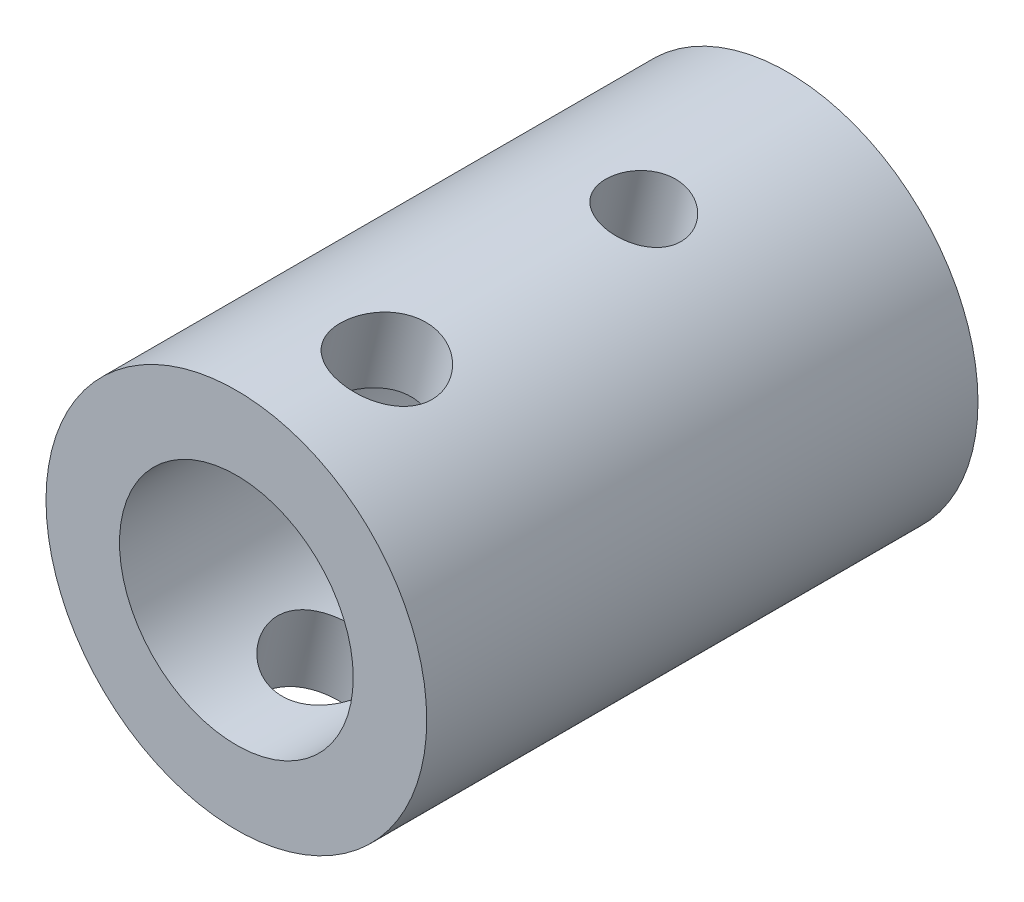
SolidWorks part; units mm, degrees
ref_plane "Front Plane" through (0, 0, 0) normal (0, 0, 1) x (1, 0, 0)
ref_plane "Top Plane" through (0, 0, 0) normal (0, 1, 0) x (1, 0, 0)
ref_plane "Right Plane" through (0, 0, 0) normal (1, 0, 0) x (0, 0, -1)
sketch "Sketch1" plane through (0, 0, 0) normal (0, 0, 1) x (1, 0, 0)
  circle A0 centre (0, 0) radius 25.9
extrude "Boss-Extrude1" add sketch "Sketch1" along normal blind 75
sketch "Sketch2" plane through (0, 0, 75) normal (0, 0, 1) x (1, 0, 0)
  circle A0 centre (0, 0) radius 15.9
extrude "Cut-Extrude1" cut sketch "Sketch2" against normal blind 75
hole_wizard "Ø10.5 (10.5) Diameter Hole1" positions "3DSketch1" profile "Sketch3" hole size "Ø10.5" standard "Ansi Metric"
sketch3d "3DSketch1"
  line L0 (0, 0, 0) -> (5.4829, 25.313, 0)
  line L3 (5.4829, 25.313, 0) -> (5.4829, 25.313, 25)
  circle A0 centre (0, 0, 0) radius 25.9 construction
  point P0 (5.4829, 25.313, 25)
  point P7 (0, 0, 25.9)
  dimension "D1" = 25
sketch "Sketch3" plane through (5.4829, 25.313, 25) normal (0, 0, 1) x (-0.9773, 0.2117, 0)
  line L0 (0, 0) -> (0, 23.1545)
  line L1 (0, 23.1545) -> (5.25, 20)
  line L2 (5.25, 20) -> (5.25, 0)
  line L5 (5.25, 0) -> (0, 0)
  line L10 (0, 23.1545) -> (-5.25, 20) construction
  line L11 (0, -6.35) -> (0, 107.95) construction
  dimension "Hole Dia." = 10.5
  dimension "Hole Depth" = 20
  dimension "Drill Angle" = 118
hole_wizard "Ø12.8 (12.8) Diameter Hole1" positions "3DSketch2" profile "Sketch4" hole size "Ø12.8" standard "Ansi Metric"
sketch3d "3DSketch2"
  line L0 (5.5559, 25.2971, 19.7505) -> (5.5559, 25.2971, 0)
  line L3 (5.5559, 25.2971, 0) -> (5.5559, 25.2971, 60)
  circle A0 centre (0, 0, 0) radius 25.9 construction
  spline S0 degree 3 poles (0.2381, 25.8989, 25.3478) (0.2381, 25.8989, 24.6522) (0.2731, 25.8987, 24.3104) (0.3755, 25.8973, 23.8062) (0.4181, 25.8967, 23.6396) (0.5203, 25.8948, 23.3094) (0.5802, 25.8936, 23.1455) (0.7815, 25.8886, 22.669) (0.9455, 25.8835, 22.3678) (1.3316, 25.8665, 21.7978) (1.5552, 25.8544, 21.5287) (2.042, 25.8205, 21.0458) (2.3071, 25.7987, 20.8288) (2.8814, 25.7408, 20.445) (3.1849, 25.7054, 20.2825) (3.6555, 25.6412, 20.0858) (3.8154, 25.618, 20.0279) (4.1411, 25.5673, 19.9277) (4.308, 25.5398, 19.8852) (4.8093, 25.4518, 19.7838) (5.1443, 25.3863, 19.7502) (5.8155, 25.241, 19.7498) (6.155, 25.1603, 19.7841) (6.8081, 24.9915, 19.9184) (7.1242, 24.903, 20.0178) (7.5831, 24.7655, 20.2157) (7.7339, 24.7188, 20.2901) (8.024, 24.6262, 20.4524) (8.1642, 24.58, 20.5405) (8.5701, 24.4427, 20.8251) (8.8229, 24.3522, 21.0431) (9.2848, 24.1798, 21.5309) (9.4891, 24.0999, 21.795) (9.8469, 23.9559, 22.3626) (10.0015, 23.8914, 22.67) (10.2483, 23.7866, 23.3044) (10.3415, 23.7459, 23.6316) (10.4678, 23.6905, 24.3063) (10.5, 23.6762, 24.6548) (10.5002, 23.676, 25.3409) (10.4693, 23.6898, 25.6826) (10.3431, 23.7452, 26.3629) (10.2491, 23.7862, 26.6927) (10.0651, 23.8644, 27.1668) (9.9965, 23.8932, 27.3218) (9.8443, 23.9563, 27.6253) (9.7603, 23.9907, 27.7744) (9.4907, 24.0993, 28.203) (9.2865, 24.1791, 28.4668) (8.8288, 24.35, 28.9512) (8.5731, 24.4417, 29.1726) (8.0314, 24.6249, 29.5529) (7.7435, 24.7174, 29.7146) (7.2844, 24.855, 29.9134) (7.1267, 24.9008, 29.9723) (6.8091, 24.9895, 30.0725) (6.6484, 25.0327, 30.1143) (6.1604, 25.159, 30.2151) (5.8253, 25.2388, 30.2498) (5.1477, 25.3857, 30.2502) (4.8125, 25.4512, 30.2165) (4.1491, 25.5677, 30.083) (3.8177, 25.6191, 29.9816) (3.1873, 25.7051, 29.7188) (2.8864, 25.7403, 29.5578) (2.4571, 25.7836, 29.2717) (2.3171, 25.7965, 29.1683) (2.05, 25.8191, 28.9503) (1.9225, 25.8288, 28.8355) (1.5574, 25.8543, 28.4738) (1.3371, 25.8662, 28.2096) (0.9468, 25.8834, 27.6348) (0.7827, 25.8885, 27.3331) (0.5153, 25.8952, 26.7018) (0.4114, 25.8968, 26.3686) (0.2731, 25.8987, 25.6911) (0.2381, 25.8989, 25.3478) (0.2381, 25.8989, 24.6522) (0.2731, 25.8987, 24.3104) knots -0.03125 -0.03125 0 0 0.03125 0.03125 0.046875 0.046875 0.0625 0.0625 0.09375 0.09375 0.125 0.125 0.15625 0.15625 0.1875 0.1875 0.203125 0.203125 0.21875 0.21875 0.25 0.25 0.28125 0.28125 0.3125 0.3125 0.328125 0.328125 0.34375 0.34375 0.375 0.375 0.40625 0.40625 0.4375 0.4375 0.46875 0.46875 0.5 0.5 0.53125 0.53125 0.5625 0.5625 0.578125 0.578125 0.59375 0.59375 0.625 0.625 0.65625 0.65625 0.6875 0.6875 0.703125 0.703125 0.71875 0.71875 0.75 0.75 0.78125 0.78125 0.8125 0.8125 0.84375 0.84375 0.859375 0.859375 0.875 0.875 0.90625 0.90625 0.9375 0.9375 0.96875 0.96875 1 1 1.03125 1.03125 1.046875 only from (0.2381, 25.8989, 25) to (0.2381, 25.8989, 25) construction
  point P0 (5.5559, 25.2971, 60)
  point P6 (0, 0, 25.9)
  dimension "D1" = 60
sketch "Sketch4" plane through (5.5559, 25.2971, 60) normal (0, 0, 1) x (-0.9767, 0.2145, 0)
  line L0 (0, 0) -> (0, 303.8455)
  line L1 (0, 303.8455) -> (6.4, 300)
  line L2 (6.4, 300) -> (6.4, 0)
  line L5 (6.4, 0) -> (0, 0)
  line L10 (0, 303.8455) -> (-6.4, 300) construction
  line L11 (0, -6.35) -> (0, 107.95) construction
  dimension "Hole Dia." = 12.8
  dimension "Hole Depth" = 300
  dimension "Drill Angle" = 118
